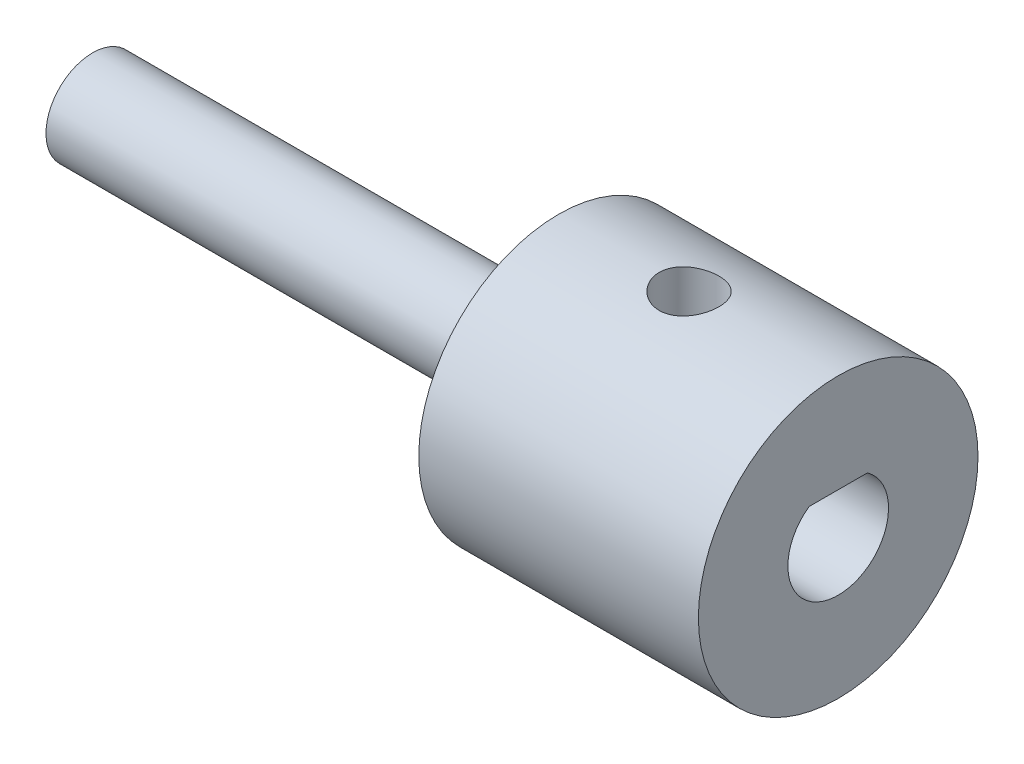
SolidWorks part; units mm, degrees
ref_plane "Front Plane" through (0, 0, 0) normal (0, 0, 1) x (1, 0, 0)
ref_plane "Top Plane" through (0, 0, 0) normal (0, 1, 0) x (1, 0, 0)
ref_plane "Right Plane" through (0, 0, 0) normal (1, 0, 0) x (0, 0, -1)
sketch "Sketch2" plane through (0, 0, 0) normal (0, 0, 1) x (1, 0, 0)
  line L0 (15, 0) -> (15, 7.5)
  line L1 (22, 0) -> (-22, 0) construction
  line L2 (15, 7.5) -> (0, 7.5)
  line L3 (0, 7.5) -> (0, 2.5)
  line L4 (0, 2.5) -> (-25, 2.5)
  line L5 (-25, 2.5) -> (-25, 0)
  line L6 (0, -4.125) -> (0, 4.125) construction
  line L7 (15, 0) -> (-25, 0) construction
  line L8 (15, 0) -> (-25, 0)
  point P10 (0, 5)
  point P11 (-25, 1.25)
  dimension "D1" = 7.5
  dimension "D2" = 2.5
  dimension "D3" = 15
  dimension "D4" = 40
revolve "Revolve1" add sketch "Sketch2" angle 360 about L7
sketch "Sketch3" plane through (15, 0, 0) normal (1, 0, 0) x (0, 0, -1)
  line L0 (-1.5, 2) -> (1.5, 2) construction
  line L1 (8.25, 0) -> (-8.25, 0) construction
  line L2 (-1.5652, 2.2) -> (1.5652, 2.2)
  arc A0 (-1.5, 2) -> (1.5, 2) centre (0, 0) ccw construction
  arc A2 (-1.5652, 2.2) -> (1.5652, 2.2) centre (0, 0) ccw
  dimension "D1" = 5
  dimension "D2" = 2
  dimension "D3" = 0.2
extrude "Cut-Extrude1" cut sketch "Sketch3" against normal blind 10
sketch "Sketch5" plane through (0, 0, 0) normal (0, 1, 0) x (1, 0, 0)
  line L0 (-8.25, 0) -> (8.25, 0) construction
  line L1 (15, -7.5) -> (15, 7.5) construction
  circle A0 centre (7, 0) radius 1.6
  dimension "D1" = 8
  dimension "D2" = 3.2
extrude "Cut-Extrude2" cut sketch "Sketch5" along normal blind 11
